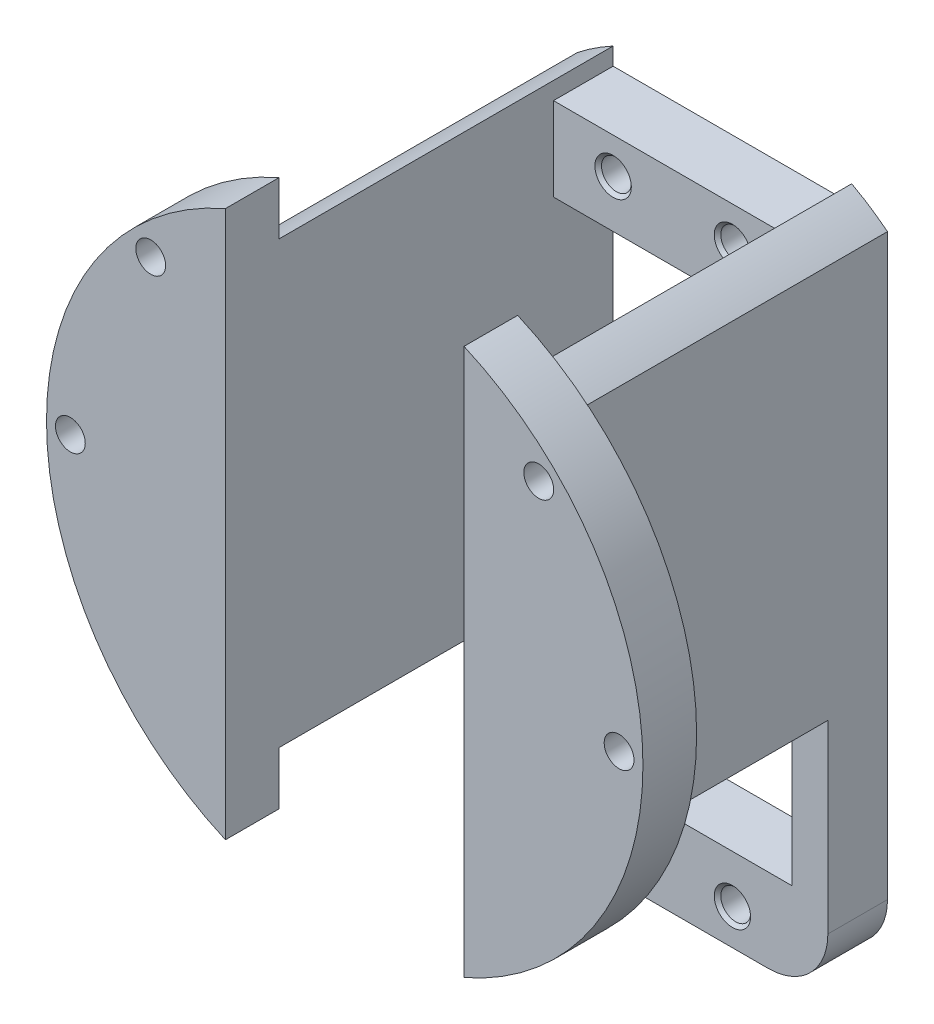
SolidWorks part; units mm, degrees
material "ПК/АБС"
ref_plane "Спереди" through (0, 0, 0) normal (0, 0, 1) x (1, 0, 0)
ref_plane "Сверху" through (0, 0, 0) normal (0, 1, 0) x (1, 0, 0)
ref_plane "Справа" through (0, 0, 0) normal (1, 0, 0) x (0, 0, -1)
sketch "Эскиз1" plane through (0, 0, 0) normal (0, 0, 1) x (1, 0, 0)
  line L0 (0, 0) -> (0, 23258.0729) construction
  line L1 (0, 0) -> (23258.0729, 0) construction
  line L2 (-10, 10) -> (10, 10)
  line L3 (10, 10) -> (10, -30)
  line L4 (10, -30) -> (-10, -30)
  line L5 (-10, -30) -> (-10, 10)
  line L6 (-13, 17) -> (13, 17)
  line L7 (13, 17) -> (13, -37)
  line L8 (13, -37) -> (-13, -37)
  line L9 (-13, -37) -> (-13, 17)
  point P7 (0, -30)
  dimension "D1" = 20
  dimension "D2" = 40
  dimension "D3" = 10
  dimension "D4" = 7
  dimension "D5" = 7
  dimension "D6" = 3
  dimension "D7" = 3
extrude "Бобышка-Вытянуть1" add sketch "Эскиз1" along normal blind 5
sketch "Эскиз2" plane through (0, 0, 0) normal (0, 0, 1) x (1, 0, 0)
  line L0 (10, -18.4662) -> (10, 18.4662)
  line L1 (10, -30) -> (10, 10) construction
  line L2 (-10, -18.4662) -> (-10, 18.4662)
  line L3 (-10, 10) -> (-10, -30) construction
  line L4 (-13, -16.4924) -> (-13, 16.4924)
  line L5 (-13, 17) -> (-13, -37) construction
  line L6 (13, 16.4924) -> (13, -16.4924)
  line L7 (13, -37) -> (13, 17) construction
  arc A0 (-10, 18.4662) -> (-13, 16.4924) centre (0, 0) ccw
  arc A1 (10, -18.4662) -> (13, -16.4924) centre (0, 0) ccw
  arc A2 (-13, -16.4924) -> (-10, -18.4662) centre (0, 0) ccw
  arc A3 (13, 16.4924) -> (10, 18.4662) centre (0, 0) ccw
  dimension "D1" = 42
extrude "Бобышка-Вытянуть2" add sketch "Эскиз2" along normal blind 28
sketch "Эскиз3" plane through (0, 0, 28) normal (0, 0, 1) x (1, 0, 0)
  line L0 (-21, 0) -> (21, 0) construction
  line L1 (-13, -21.3826) -> (-13, -50021.3826) construction
  line L2 (-13, -16.4924) -> (-13, -37) construction
  line L3 (13, -21.1704) -> (13, -50021.1704) construction
  line L4 (13, -37) -> (13, -16.4924) construction
  line L5 (-13, -16.4924) -> (-13, -37)
  line L6 (-13, -37) -> (13, -37)
  line L7 (13, -37) -> (13, -16.4924)
  circle A0 centre (0, 0) radius 21 construction
  arc A10 (-13, -16.4924) -> (13, -16.4924) centre (0, 0) cw
  point P9 (-13, -26.7462)
  point P16 (13, -26.7462)
  point P25 (0, 0)
  dimension "D2" = 42
extrude "Вырез-Вытянуть1" cut sketch "Эскиз3" against normal through all flip side to cut
fillet "Скругление1" radius 5 2 edges at (-13, -37, 2.5) (13, -37, 2.5)
sketch "Эскиз7" plane through (0, 0, 28) normal (0, 0, 1) x (1, 0, 0)
  line L2 (-10, -22.9129) -> (-10, 22.9129)
  line L3 (10, -22.9129) -> (10, 22.9129)
  line L4 (10, -30) -> (10, -18.4662) construction
  line L5 (-10, -18.4662) -> (-10, -30) construction
  arc A2 (-10, 22.9129) -> (-10, -22.9129) centre (0, 0) ccw
  arc A3 (10, -22.9129) -> (10, 22.9129) centre (0, 0) ccw
  dimension "D1" = 50
extrude "Бобышка-Вытянуть3" add sketch "Эскиз7" along normal blind 4.5
hole_wizard "Отверстие обработанное метчиком M3x0.51" positions "Эскиз4" profile "Эскиз5" tap size "M3x0.5" standard "HASCO Metric" end condition through all
sketch "Эскиз4" plane through (0, 0, 5) normal (0, 0, 1) x (1, 0, 0)
  line L0 (0, 0) -> (0, 50000) construction
  line L1 (0, -10) -> (-50000, -10) construction
  line L2 (10, 10) -> (-10, 10) construction
  line L4 (0, 14) -> (-50000, 14) construction
  line L5 (-5, -10) -> (-5, 49990) construction
  point P0 (-5, 14)
  dimension "D1" = 20
  dimension "D2" = 24
  dimension "D3" = 5
sketch "Эскиз5" plane through (-5, 14, 5) normal (1, 0, 0) x (0, -1, 0)
  line L0 (0, 0) -> (0, 5)
  line L1 (0, 5) -> (1.25, 5)
  line L2 (1.25, 5) -> (1.25, 0.275)
  line L3 (1.25, 0.275) -> (1.525, 0)
  line L5 (1.525, 0) -> (0, 0)
  line L6 (-1.25, 0.275) -> (-1.525, 0) construction
  line L11 (0, -6.35) -> (0, 107.95) construction
  dimension "Диаметр проходного сверла" = 2.5
  dimension "Глубина проходного сверла" = 5
  dimension "Диаметр передней зенковки" = 3.05
  dimension "Угол передней зенковки" = 90
cosmetic thread "Отверстие резьбы1" parameters "D2"=3
pattern_linear "Линейный массив1" count 2 spacing 10 along (1, 0, 0) count 2 spacing 48 along (0, -1, 0) of "Отверстие обработанное метчиком M3x0.51"
hole_wizard "Отверстие1" positions "Эскиз8" profile "Эскиз9" legacy end condition through all
sketch "Эскиз8" plane through (0, 0, 32.5) normal (0, 0, 1) x (1, 0, 0)
  line L0 (-23, 0) -> (23, 0) construction
  circle A0 centre (0, 0) radius 23 construction
  point P0 (-23, 0)
  dimension "D1" = 46
sketch "Эскиз9" plane through (-23, 0, 32.5) normal (1, 0, 0) x (0, -1, 0)
  line L0 (0, 0) -> (0, 32.5)
  line L1 (0, 32.5) -> (1.25, 32.5)
  line L2 (1.25, 32.5) -> (1.25, 0)
  line L3 (1.25, 0) -> (0, 0)
  line L4 (0, 110) -> (0, -10) construction
  dimension "Диаметр" = 2.5
  dimension "Глубина" = 32.5
pattern_circular "Круговой массив1" count 8 over 360 about axis through (0, 0, 32.5) along (0, 0, 1) skipping 1, 2, 3, 6 of "Отверстие1"
